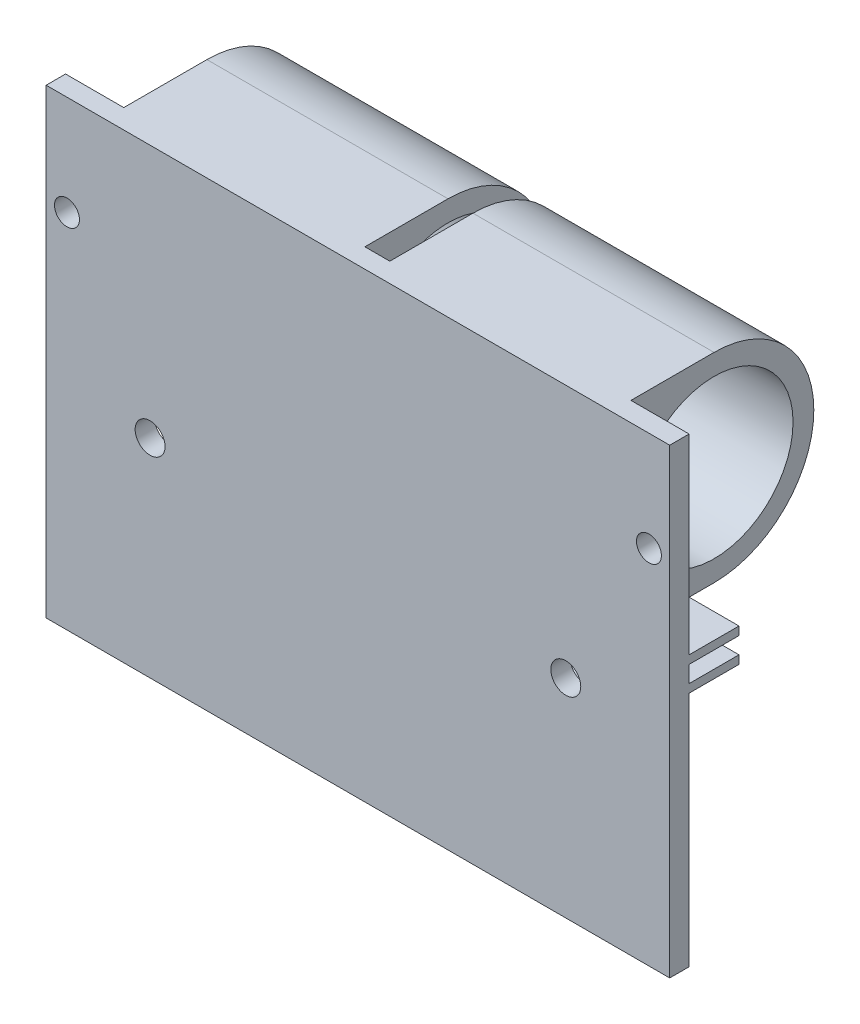
SolidWorks part; units mm, degrees
material "1060 Alloy"
ref_plane "Front Plane" through (0, 0, 0) normal (0, 0, 1) x (1, 0, 0)
ref_plane "Top Plane" through (0, 0, 0) normal (0, 1, 0) x (1, 0, 0)
ref_plane "Right Plane" through (0, 0, 0) normal (1, 0, 0) x (0, 0, -1)
sketch "Sketch1" plane through (0, 0, 0) normal (0, 0, 1) x (1, 0, 0)
  line L0 (-37.5, 0) -> (-25, 0) construction
  line L1 (37.5, -10.5) -> (30, -10.5)
  line L2 (37.5, -10.5) -> (37.5, 10.5)
  line L3 (37.5, 10.5) -> (-37.5, 10.5)
  line L4 (-37.5, -10.5) -> (-37.5, 10.5)
  line L5 (37.5, -10.5) -> (-37.5, 10.5) construction
  line L6 (37.5, 10.5) -> (-37.5, -10.5) construction
  line L7 (-30, -10.5) -> (-37.5, -10.5)
  line L8 (-25, 0) -> (-12.5, 0) construction
  line L9 (-12.5, 0) -> (0, 0) construction
  line L10 (0, 0) -> (12.5, 0) construction
  line L11 (12.5, 0) -> (25, 0) construction
  line L12 (25, 0) -> (37.5, 0) construction
  line L13 (-5, -10.5) -> (-20, -10.5)
  line L14 (20, -10.5) -> (5, -10.5)
  line L15 (-35, 10.5) -> (-35, 8) construction
  line L16 (-35, 8) -> (-37.5, 8) construction
  line L17 (-25, -10.5) -> (-25, 10.5) construction
  line L18 (-12.5, -10.5) -> (-12.5, 10.5) construction
  line L19 (12.5, -10.5) -> (12.5, 10.5) construction
  arc A0 (-20, -10.5) -> (-30, -10.5) centre (-25, -10.5) cw
  arc A1 (5, -10.5) -> (-5, -10.5) centre (0, -10.5) cw
  arc A2 (30, -10.5) -> (20, -10.5) centre (25, -10.5) cw
  circle A3 centre (-25, -10.5) radius 1.7999
  circle A4 centre (0, -10.5) radius 1.7999
  circle A5 centre (25, -10.5) radius 1.7999
  circle A6 centre (-35, 8) radius 1.5
  circle A7 centre (-15, 8) radius 1.5
  circle A8 centre (-10, 8) radius 1.5
  circle A9 centre (10, 8) radius 1.5
  circle A10 centre (35, 8) radius 1.5
  circle A11 centre (15, 8) radius 1.5
  point P0 (0, 0)
  dimension "D4" = 5
  dimension "D5" = 3.5999
  dimension "D7" = 3
  dimension "D1" = 75
  dimension "D2" = 21
  dimension "D3" = 12.5
  dimension "D6" = 2.5
extrude "Boss-Extrude1" add sketch "Sketch1" along normal blind 7
ref_plane "Plane1" through (0, 2.25, 0) normal (0, 1, 0) x (1, 0, 0)
sketch "Sketch2" plane through (0, 2.25, 0) normal (0, 1, 0) x (1, 0, 0)
  line L1 (-37.5, -13.55) -> (-12.5, -13.55) construction
  line L7 (37.5, -7) -> (-37.5, -7)
  line L8 (37.5, -7) -> (37.5, -20.1)
  line L11 (37.5, -20.1) -> (-37.5, -20.1)
  line L12 (-37.5, -7) -> (-37.5, -20.1)
  line L13 (37.5, -7) -> (-37.5, -20.1) construction
  line L14 (37.5, -20.1) -> (-37.5, -7) construction
  line L15 (-12.5, -13.55) -> (12.5, -13.55) construction
  line L16 (12.5, -13.55) -> (37.5, -13.55) construction
  line L17 (12.5, -13.55) -> (12.5, -7) construction
  line L18 (-12.5, -13.55) -> (-12.5, -7) construction
  circle A0 centre (0, -13.55) radius 2.5
  circle A1 centre (6.0001, -13.55) radius 2.6999
  circle A2 centre (-6.0001, -13.55) radius 2.6999
  circle A3 centre (6.0001, -13.55) radius 1.3498
  circle A4 centre (-6.0001, -13.55) radius 1.3498
  circle A5 centre (-18.9999, -13.55) radius 1.3498
  circle A6 centre (-18.9999, -13.55) radius 2.6999
  circle A7 centre (-25, -13.55) radius 2.5
  circle A8 centre (-31.0001, -13.55) radius 1.3498
  circle A9 centre (-31.0001, -13.55) radius 2.6999
  circle A10 centre (31.0001, -13.55) radius 1.3498
  circle A11 centre (31.0001, -13.55) radius 2.6999
  circle A12 centre (25, -13.55) radius 2.5
  circle A13 centre (18.9999, -13.55) radius 1.3498
  circle A14 centre (18.9999, -13.55) radius 2.6999
  point P4 (0, -13.55)
  dimension "D2" = 5
  dimension "D3" = 5.3999
  dimension "D6" = 2.6997
  dimension "D1" = 13.1
  dimension "D4" = 6.0001
  dimension "D5" = 6.0001
  dimension "D7" = 25
extrude "Boss-Extrude2" add sketch "Sketch2" against normal blind 6.988 contours L7 L12 L11 L8 A11 A9 A7 A2 A1 A0 A6 A12 A14 | A9 A8 | A6 A5 | A2 A4 | A1 A3 | A14 A13 | A11 A10 region at (36.7386, 2.25, 13.55) region at (3.3766, 2.25, 13.55) region at (-8.6237, 2.25, 13.55) region at (-21.6234, 2.25, 13.55) region at (-33.6237, 2.25, 13.55) region at (28.3766, 2.25, 13.55) region at (16.3763, 2.25, 13.55)
extrude "Cut-Extrude1" cut sketch "Sketch2<3>" against normal blind 2.5 contours A9 A8 | A6 A5 | A2 A4 | A1 A3 | A14 A13 | A11 A10 region at (3.3766, 2.25, 13.55) region at (-8.6237, 2.25, 13.55) region at (-21.6234, 2.25, 13.55) region at (-33.6237, 2.25, 13.55) region at (28.3766, 2.25, 13.55) region at (16.3763, 2.25, 13.55)
sketch "Sketch2<3>" plane through (0, 2.25, 0) normal (0, 1, 0) x (1, 0, 0) same geometry as "Sketch2"
ref_plane "Plane2" through (-37.5, -4.738, 7) normal (-1, 0, 0) x (0, 0, 1)
sketch "Sketch5" plane through (0, 2.25, 0) normal (0, 1, 0) x (1, 0, 0)
  line L1 (-37.5, -7) -> (37.5, -7)
  line L2 (-37.5, -7) -> (-37.5, -20.1)
  line L3 (-37.5, -20.1) -> (37.5, -20.1)
  line L4 (37.5, -7) -> (37.5, -20.1)
  line L5 (-37.5, -7) -> (37.5, -20.1) construction
  line L6 (-37.5, -20.1) -> (37.5, -7) construction
  point P4 (0, -13.55)
extrude "Cut-Extrude3" cut sketch "Sketch5" against normal blind 21.082
sketch "Sketch6" plane through (0, 10.5, 0) normal (0, 1, 0) x (1, 0, 0)
  line L4 (37.5, 0) -> (-37.5, 0)
  line L5 (-37.5, 0) -> (-37.5, -7)
  line L6 (-37.5, -7) -> (37.5, -7)
  line L7 (37.5, -7) -> (37.5, 0)
  line L8 (37.5, 0) -> (-37.5, 0)
  line L9 (-37.5, 0) -> (-37.5, -7)
  line L10 (-37.5, -7) -> (37.5, -7)
  line L11 (37.5, -7) -> (37.5, 0)
  dimension "D1" = 0
extrude "Boss-Extrude3" add sketch "Sketch6" along normal blind 9.5
sketch "Sketch8" plane through (0, 0, 0) normal (0, 0, -1) x (-1, 0, 0)
  line L6 (-37.5, 20) -> (37.5, 20)
  line L8 (-37.5, 20) -> (-37.5, -18.0302)
  line L9 (-37.5, -18.0302) -> (37.5, -18.0302)
  line L10 (37.5, 20) -> (37.5, -18.0302)
  line L11 (-37.5, 20) -> (37.5, -18.0302) construction
  line L12 (-37.5, -18.0302) -> (37.5, 20) construction
  point P4 (0, 0.9849)
extrude "Cut-Extrude4" cut sketch "Sketch8" against normal blind 4.666
ref_plane "Plane4" through (0, -35.5, 0) normal (0, -1, 0) x (-1, 0, 0)
sketch "Sketch10" plane through (0, -35.5, 0) normal (0, -1, 0) x (-1, 0, 0)
  line L1 (-37.5, -7) -> (37.5, -7)
  line L2 (-37.5, -7) -> (-37.5, -4.666)
  line L3 (-37.5, -4.666) -> (37.5, -4.666)
  line L4 (37.5, -7) -> (37.5, -4.666)
  line L5 (-37.5, -7) -> (37.5, -4.666) construction
  line L6 (-37.5, -4.666) -> (37.5, -7) construction
  point P4 (0, -5.833)
extrude "Boss-Extrude5" add sketch "Sketch10" against normal up to surface (25 mm away) up to face at (12.5, -10.5, 5.833)
sketch "Sketch11" plane through (0, 0, 4.666) normal (0, 0, -1) x (-1, 0, 0)
  circle A0 centre (-25, -10.5) radius 1.7999
  circle A1 centre (0, -10.5) radius 1.7999
  circle A2 centre (25, -10.5) radius 1.7999
extrude "Cut-Extrude5" cut sketch "Sketch11" against normal blind 5
sketch "Sketch15" plane through (0, 0, 7) normal (0, 0, 1) x (1, 0, 0)
  line L1 (-20.5223, 1.9953) -> (24.1312, 1.9953)
  line L2 (-20.5223, 1.9953) -> (-20.5223, 15.6126)
  line L3 (-20.5223, 15.6126) -> (24.1312, 15.6126)
  line L4 (24.1312, 1.9953) -> (24.1312, 15.6126)
  line L5 (-20.5223, 1.9953) -> (24.1312, 15.6126) construction
  line L6 (-20.5223, 15.6126) -> (24.1312, 1.9953) construction
  line L7 (-7.3653, -8.2939) -> (4.3629, -8.2939)
  line L8 (-7.3653, -8.2939) -> (-7.3653, -14.2814)
  line L9 (-7.3653, -14.2814) -> (4.3629, -14.2814)
  line L10 (4.3629, -8.2939) -> (4.3629, -14.2814)
  line L11 (-7.3653, -8.2939) -> (4.3629, -14.2814) construction
  line L12 (-7.3653, -14.2814) -> (4.3629, -8.2939) construction
  point P4 (1.8044, 8.8039)
  point P9 (-1.5012, -11.2877)
extrude "Boss-Extrude7" add sketch "Sketch15" against normal up to surface (2.334 mm away) up to face at (23.2001, -10.5, 4.666)
ref_plane "Plane5" through (30.5, 0, 0) normal (1, 0, 0) x (0, 0, -1)
sketch "Sketch16" plane through (30.5, 0, 0) normal (1, 0, 0) x (0, 0, -1)
  line L0 (-4.666, 6.5) -> (-4.666, 9.5) construction
  line L1 (-4.666, 6.5) -> (-4.666, 9.5)
  line L2 (-4.666, 20) -> (-4.666, -35.5) construction
  line L3 (5.334, 20) -> (-4.666, 20)
  line L4 (5.334, -4) -> (-4.666, -4)
  line L5 (-4.666, 20) -> (-4.666, -4)
  circle A0 centre (5.334, 8) radius 9.5
  arc A1 (5.334, -4) -> (5.334, 20) centre (5.334, 8) ccw
  circle A3 centre (5.334, 8) radius 12 construction
  point P5 (-4.666, 8)
  point P13 (16.834, 8)
  dimension "D1" = 19
  dimension "D3" = 10
  dimension "D2" = 2.5
extrude "Boss-Extrude9" add sketch "Sketch16" against normal blind 29 separate body contours L4 A1 L3 L5 L1 A0 region at (30.5, 8, 4.3404)
mirror "Mirror1" about plane through (0, 0, 0) normal (1, 0, 0) of bodies 114
combine bodies "Combine1" operation type add bodies to combine 115 114 113
sketch "Sketch17" plane through (0, 0, 0) normal (1, 0, 0) x (0, 0, -1)
  line L0 (-4.666, -35.5) -> (-7, -35.5) construction
  line L1 (5.334, -35.5) -> (-4.666, -35.5)
  line L3 (5.334, -11.5) -> (-4.666, -11.5)
  line L4 (-4.666, 20) -> (-4.666, -35.5) construction
  line L5 (-4.666, -11.5) -> (-4.666, -35.5)
  circle A2 centre (5.334, 8) radius 9.5 construction
  circle A3 centre (5.334, 8) radius 9.5 construction
  circle A5 centre (5.334, -23.5) radius 9.5
  arc A6 (5.334, -35.5) -> (5.334, -11.5) centre (5.334, -23.5) ccw
  circle A8 centre (5.334, -23.5) radius 12 construction
  point P2 (16.8097, -12.4915)
  point P3 (5.334, -16)
  point P13 (16.8097, -19.9915)
  dimension "D1" = 19
  dimension "D2" = 2.5
extrude "Boss-Extrude11" add sketch "Sketch17" along normal mid plane 29
sketch "Sketch18" plane through (0, 0, 4.666) normal (0, 0, -1) x (-1, 0, 0)
  line L0 (-14.5, -11.5) -> (-14.5, -35.5) construction
  line L1 (-14.5, -14) -> (-14.5, -33) construction
  line L2 (-14.5, -11.5) -> (-14.5, -35.5)
  line L3 (-14.5, -14) -> (-14.5, -33)
  line L4 (-30.5, 20) -> (-30.5, -4) construction
  line L5 (-30.5, 20) -> (-30.5, -4)
  line L6 (-30.5, -4) -> (-37.5, -4)
  line L7 (-37.5, 20) -> (-37.5, -35.5) construction
  line L8 (-37.5, -4) -> (-37.5, -6)
  line L9 (-37.5, -6) -> (-21.77, -6)
  line L10 (-1.5, -4) -> (-30.5, -4) construction
  line L11 (-21.77, -6) -> (-21.77, -7.0074)
  line L12 (-37.5, -7) -> (-22.77, -7)
  line L13 (-22.77, -7) -> (-22.77, -7.0074)
  line L14 (-18.7626, -4) -> (-16.114, -4)
  line L15 (-37.5, -3) -> (-30.5, -3)
  line L16 (-37.5, -3) -> (-37.5, -4)
  circle A1 centre (-18.7626, -7.0074) radius 1.5
  arc A2 (-18.7626, -4) -> (-21.77, -7.0074) centre (-18.7626, -7.0074) cw
  arc A3 (-16.114, -4) -> (-22.77, -7.0074) centre (-18.7626, -7.0074) cw
  arc A5 (-18.7626, -3) -> (-22.77, -7.0074) centre (-18.7626, -7.0074) cw construction
  line M15 (-1.5, -4) -> (-30.5, -4)
  line M16 (-30.5, -4) -> (-30.5, 20)
  line M18 (-37.5, 20) -> (-37.5, -35.5)
  dimension "D2" = 3
  dimension "D3" = 1
  dimension "D1" = 2
  dimension "D4" = 1
extrude "Boss-Extrude12" add sketch "Sketch18" along normal blind 6 separate body contours L15 L6 M18 M16 | A3 A2 L11 L9 L12 L13 M15 M18 | A1 region at (34, -3.5, 4.666) region at (17.4383, -4.238, 4.666) region at (18.7626, -7.0074, 4.666)
mirror "Mirror2" about plane through (0, 0, 0) normal (1, 0, 0) of bodies 121 119 120
combine bodies "Combine2" operation type add bodies to combine 122 124 120 119 121 118 123
